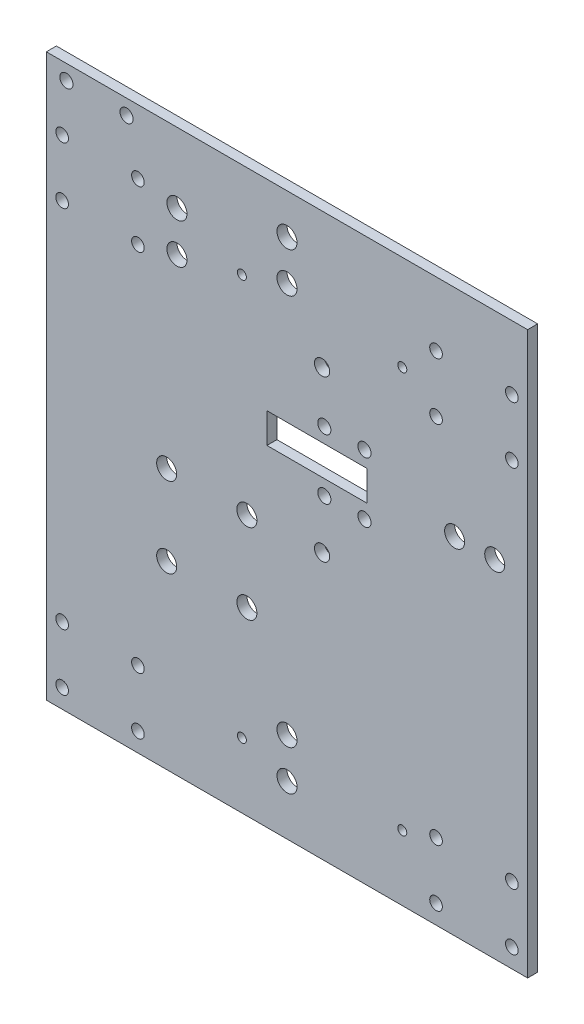
SolidWorks part; units mm, degrees
ref_plane "Front Plane" through (0, 0, 0) normal (0, 0, 1) x (1, 0, 0)
ref_plane "Top Plane" through (0, 0, 0) normal (0, 1, 0) x (1, 0, 0)
ref_plane "Right Plane" through (0, 0, 0) normal (1, 0, 0) x (0, 0, -1)
sketch "Sketch1" plane through (0, 0, 0) normal (0, 0, 1) x (1, 0, 0)
  line L0 (76.2, 177.8) -> (76.2, 0) construction
  line L1 (0, 0) -> (152.4, 0)
  line L2 (0, 0) -> (0, 177.8)
  line L3 (0, 177.8) -> (152.4, 177.8)
  line L4 (152.4, 0) -> (152.4, 177.8)
  line L5 (38.1, 82.55) -> (63.5, 82.55) construction
  line L6 (101.6, 104.775) -> (69.85, 104.775)
  line L7 (101.6, 104.775) -> (101.6, 114.3)
  line L8 (101.6, 114.3) -> (69.85, 114.3)
  line L9 (69.85, 104.775) -> (69.85, 114.3)
  line L10 (38.1, 57.15) -> (63.5, 57.15) construction
  line L11 (50.8, 82.55) -> (50.8, 57.15) construction
  line L12 (101.6, 109.5375) -> (135.289, 109.5375) construction
  line L13 (69.85, 109.5375) -> (101.6, 109.5375) construction
  line L14 (87.3125, 114.3) -> (87.3125, 104.775) construction
  circle A0 centre (38.1, 82.55) radius 3.175
  circle A1 centre (63.5, 82.55) radius 3.175
  circle A2 centre (38.1, 57.15) radius 3.175
  circle A3 centre (63.5, 57.15) radius 3.175
  circle A4 centre (88.0237, 100.0125) radius 2.0828
  circle A5 centre (100.7237, 100.0125) radius 2.0828
  circle A6 centre (88.0237, 119.0625) radius 2.0828
  circle A7 centre (100.7237, 119.0625) radius 2.0828
  circle A8 centre (129.286, 109.5375) radius 3.175
  circle A9 centre (123.4, 139.48) radius 2
  circle A10 centre (147.4, 139.48) radius 2
  circle A11 centre (123.4, 157.48) radius 2
  circle A12 centre (147.4, 157.48) radius 2
  circle A13 centre (5, 6) radius 2
  circle A14 centre (29, 6) radius 2
  circle A15 centre (5, 24) radius 2
  circle A16 centre (29, 24) radius 2
  circle A17 centre (5, 139.48) radius 2
  circle A18 centre (29, 139.48) radius 2
  circle A19 centre (5, 157.48) radius 2
  circle A20 centre (29, 157.48) radius 2
  circle A21 centre (123.4, 6) radius 2
  circle A22 centre (147.4, 6) radius 2
  circle A23 centre (123.4, 24) radius 2
  circle A24 centre (147.4, 24) radius 2
  circle A25 centre (41.35, 155.575) radius 3.175
  circle A26 centre (41.35, 142.875) radius 3.175
  circle A27 centre (6.35, 173.0375) radius 2.0828
  circle A28 centre (25.4, 173.0375) radius 2.0828
  circle A29 centre (141.986, 109.5375) radius 3.175
  circle A30 centre (87.3125, 84.1375) radius 2.413
  circle A31 centre (87.3125, 134.9375) radius 2.413
  circle A32 centre (61.9125, 147.6375) radius 1.4224
  circle A33 centre (112.7125, 147.6375) radius 1.4224
  circle A34 centre (112.7125, 20.6375) radius 1.4224
  circle A35 centre (61.9125, 20.6375) radius 1.4224
  circle A36 centre (76.2, 28.575) radius 3.175
  circle A37 centre (76.2, 15.875) radius 3.175
  circle A38 centre (76.2, 165.1) radius 3.175
  circle A39 centre (76.2, 152.4) radius 3.175
  dimension "D4" = 6.35
  dimension "D7" = 57.15
  dimension "D10" = 24
  dimension "D12" = 4
  dimension "D15" = 4
  dimension "D8" = 38.1
  dimension "D9" = 4
  dimension "D18" = 4
  dimension "D25" = 6.35
  dimension "D29" = 4.1656
  dimension "D37" = 4.1656
  dimension "D39" = 18.1737
  dimension "D42" = 6.35
  dimension "D43" = 12.7
  dimension "D44" = 27.686
  dimension "D45" = 4.826
  dimension "D49" = 2.8448
  dimension "D54" = 6.35
  dimension "D57" = 15.875
  dimension "D1" = 152.4
  dimension "D2" = 177.8
  dimension "D5" = 25.4
  dimension "D6" = 25.4
  dimension "D11" = 18
  dimension "D13" = 24
  dimension "D14" = 18
  dimension "D16" = 24
  dimension "D17" = 18
  dimension "D19" = 24
  dimension "D20" = 18
  dimension "D21" = 5
  dimension "D22" = 5
  dimension "D23" = 6
  dimension "D24" = 20.32
  dimension "D26" = 12.7
  dimension "D27" = 22.225
  dimension "D28" = 12.35
  dimension "D30" = 19.05
  dimension "D31" = 6.35
  dimension "D32" = 4.7625
  dimension "D33" = 31.75
  dimension "D34" = 9.525
  dimension "D35" = 19.05
  dimension "D36" = 22.225
  dimension "D38" = 12.7
  dimension "D40" = 4.7625
  dimension "D41" = 4.7625
  dimension "D46" = 50.8
  dimension "D47" = 50.8
  dimension "D48" = 14.2875
  dimension "D50" = 14.2875
  dimension "D51" = 127
  dimension "D52" = 38.1
  dimension "D53" = 50.8
  dimension "D55" = 12.7
  dimension "D56" = 12.7
  dimension "D58" = 12.7
  dimension "D59" = 25.4
extrude "Boss-Extrude1" add sketch "Sketch1" along normal blind 3.175
